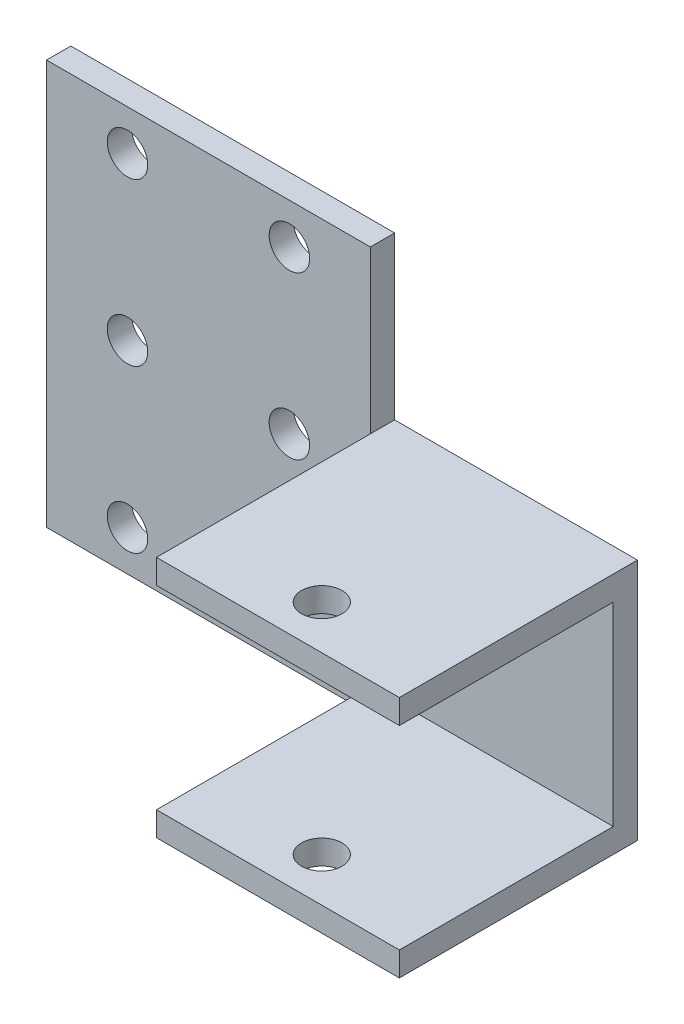
SolidWorks part; units mm, degrees
ref_plane "Front Plane" through (0, 0, 0) normal (0, 0, 1) x (1, 0, 0)
ref_plane "Top Plane" through (0, 0, 0) normal (0, 1, 0) x (1, 0, 0)
ref_plane "Right Plane" through (0, 0, 0) normal (1, 0, 0) x (0, 0, -1)
sketch "Sketch1" plane through (0, 0, 0) normal (0, 0, 1) x (1, 0, 0)
  line L0 (20, 50) -> (20, 0) construction
  line L1 (0, 0) -> (40, 0)
  line L2 (0, 0) -> (0, 50)
  line L3 (0, 50) -> (40, 50)
  line L4 (40, 0) -> (40, 50)
  line L5 (30, 45) -> (10, 45) construction
  line L6 (30, 45) -> (30, 25) construction
  line L7 (30, 45) -> (30, 50) construction
  line L8 (30, 5) -> (30, 0) construction
  circle A0 centre (30, 45) radius 2.5
  circle A1 centre (10, 45) radius 2.5
  circle A2 centre (10, 25) radius 2.5
  circle A3 centre (10, 5) radius 2.5
  circle A4 centre (30, 25) radius 2.5
  circle A5 centre (30, 5) radius 2.5
  point P9 (20, 45)
  point P24 (29.7165, 25)
  dimension "D7" = 5
  dimension "D1" = 50
  dimension "D2" = 40
  dimension "D5" = 20
  dimension "D6" = 5
  dimension "D3" = 2
  dimension "D4" = 3
extrude "Boss-Extrude1" add sketch "Sketch1" along normal blind 3
sketch "Sketch2" plane through (40, 0, 0) normal (1, 0, 0) x (0, 0, -1)
  line L0 (-3, 0) -> (-3, 50) construction
  line L1 (0, 0) -> (-29.4143, 0)
  line L2 (0, 0) -> (0, 30.0041)
  line L3 (0, 30.0041) -> (-29.4143, 30.0041)
  line L4 (-29.4143, 0) -> (-29.4143, 3)
  line L5 (-29.4143, 27.0041) -> (-3, 27.0041)
  line L7 (-29.4143, 3) -> (-3, 3)
  line L8 (-3, 27.0041) -> (-3, 3)
  line L9 (-29.4143, 27.0041) -> (-29.4143, 30.0041)
  point P11 (-40.2936, 8.7684)
  dimension "D1" = 3
extrude "Boss-Extrude2" add sketch "Sketch2" along normal blind 30
sketch "Sketch3" plane through (0, 27.0041, 0) normal (0, -1, 0) x (1, 0, 0)
  line L0 (70, 3) -> (40, 3) construction
  line L2 (55, 24) -> (55, 29.4143) construction
  line L3 (70, 29.4143) -> (40, 29.4143) construction
  circle A0 centre (55, 24) radius 2.5
  dimension "D1" = 5
  dimension "D2" = 21
extrude "Cut-Extrude1" cut sketch "Sketch3" against normal through all both and the other way through all
